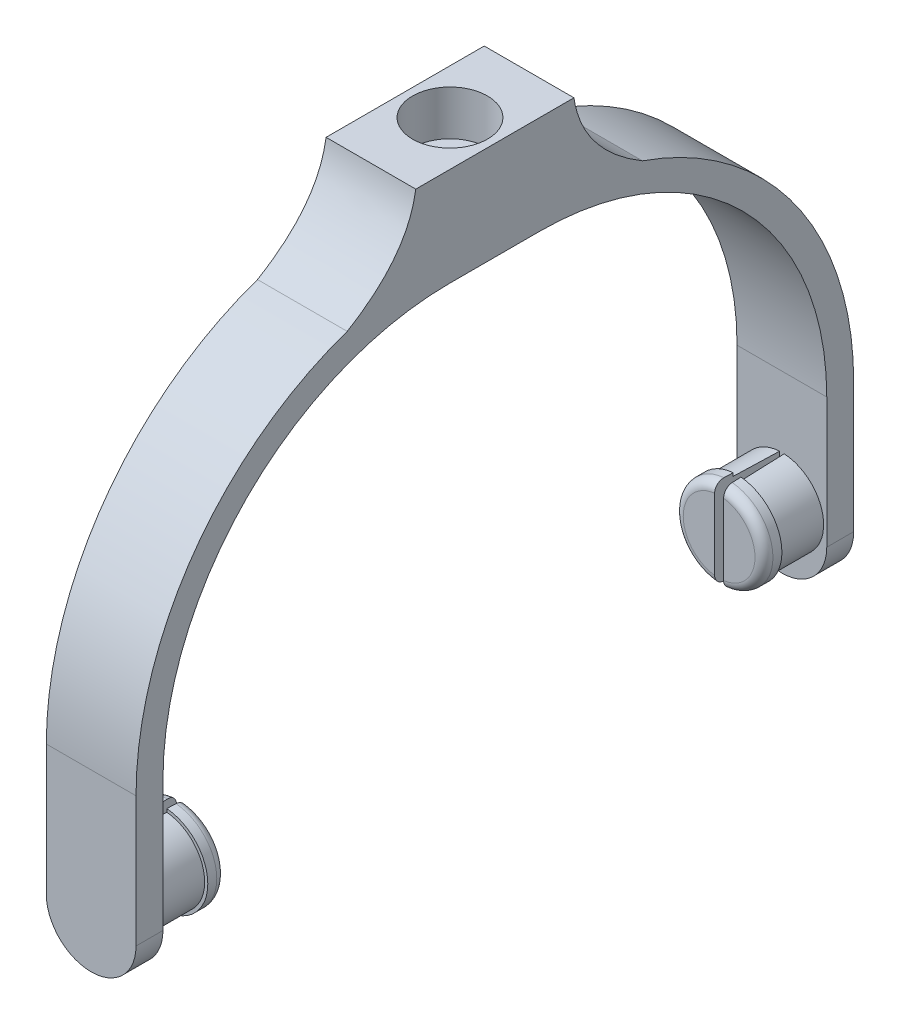
SolidWorks part; units mm, degrees
ref_plane "Front Plane" through (0, 0, 0) normal (0, 0, 1) x (1, 0, 0)
ref_plane "Top Plane" through (0, 0, 0) normal (0, 1, 0) x (1, 0, 0)
ref_plane "Right Plane" through (0, 0, 0) normal (1, 0, 0) x (0, 0, -1)
sketch "Sketch3" plane through (0, 0, 0) normal (1, 0, 0) x (0, 0, -1)
  line L0 (-37, -7) -> (-37, 12.5)
  line L5 (-40, -7) -> (-40, 12.5)
  line L6 (-5, 47.5) -> (5, 47.5)
  line L7 (-5, 44.5) -> (5, 44.5)
  line L8 (37, -7) -> (37, 12.5)
  line L10 (40, -7) -> (40, 12.5)
  line L12 (-37, -7) -> (-40, -7)
  line L13 (37, -7) -> (40, -7)
  line L14 (40, -10) -> (40, 12.5) construction
  line L15 (-40, -10) -> (-40, 12.5) construction
  line L17 (-40, -10) -> (40, -10) construction
  line L18 (-37, -7) -> (37, -7) construction
  arc A4 (-37, 12.5) -> (-5, 44.5) centre (-5, 12.5) cw
  arc A5 (5, 44.5) -> (37, 12.5) centre (5, 12.5) cw
  arc A6 (-40, 12.5) -> (-5, 47.5) centre (-5, 12.5) cw
  arc A7 (5, 47.5) -> (40, 12.5) centre (5, 12.5) cw
  point P0 (0, 0)
  dimension "D1" = 3
  dimension "D2" = 7
extrude "Boss-Extrude1" add sketch "Sketch3" along normal blind 10
fillet "Fillet1" radius 5 4 edges at (10, -7, -38.5) (0, -7, -38.5) (0, -7, 38.5) (10, -7, 38.5)
sketch "Sketch6" plane through (0, 0, 37) normal (0, 0, -1) x (-1, 0, 0)
  line L0 (-5, -7) -> (-5, -2.6229) construction
  circle A2 centre (-5, 0) radius 4.65
  point P0 (0, 0)
  dimension "D1" = 7
extrude "Boss-Extrude2" add sketch "Sketch6" along normal blind 5
sketch "Sketch7" plane through (0, 0, 32) normal (0, 0, -1) x (-1, 0, 0)
  circle A2 centre (-5, 0) radius 5
  circle A3 centre (-5, 0) radius 5
  point P0 (-4.7155, -0.2336)
  point P3 (-4.7155, -0.2336)
  dimension "D1" = 0.35
extrude "Boss-Extrude3" add sketch "Sketch7" along normal blind 2
fillet "Fillet2" radius 1 1 edges at (5, 5, 30)
mirror "Mirror1" about plane through (0, 0, 0) normal (0, 0, 1) of "Boss-Extrude3", "Fillet2", "Boss-Extrude2"
sketch "Sketch8" plane through (10, 0, 0) normal (1, 0, 0) x (0, 0, -1)
  line L1 (8.8152, 55.4795) -> (-8.8152, 55.4795)
  line L5 (0, 47.5) -> (0, 55.4795) construction
  line L13 (37, 12.5) -> (37, -2)
  line L14 (37, -2) -> (40, -2)
  line L15 (40, -2) -> (40, 12.5)
  line L16 (5, 47.5) -> (-5, 47.5)
  line L17 (-40, 12.5) -> (-40, -2)
  line L18 (-40, -2) -> (-37, -2)
  line L19 (-37, -2) -> (-37, 12.5)
  line L20 (-5, 44.5) -> (5, 44.5)
  line L24 (5, 47.5) -> (-5, 47.5)
  arc A0 (5, 47.5) -> (16.4608, 45.5704) centre (5, 12.5) cw
  arc A4 (40, 12.5) -> (5, 47.5) centre (5, 12.5) ccw
  arc A5 (-5, 47.5) -> (-40, 12.5) centre (-5, 12.5) ccw
  arc A6 (-5, 44.5) -> (-37, 12.5) centre (-5, 12.5) ccw
  arc A7 (37, 12.5) -> (5, 44.5) centre (5, 12.5) ccw
  arc A9 (-5, 47.5) -> (-16.4608, 45.5704) centre (-5, 12.5) ccw
  spline S0 degree 2 poles (-16.4608, 45.5704) (-9.6893, 49.5906) (-8.8152, 55.4795) knots 0 0 0 1 1 1
  spline S1 degree 2 poles (16.4608, 45.5704) (9.6893, 49.5906) (8.8152, 55.4795) knots 0 0 0 1 1 1
  dimension "D1" = 0
extrude "Boss-Extrude4" add sketch "Sketch8" against normal up to surface (10 mm away) up to face at (0, 21.146, 0)
sketch "Sketch9" plane through (0, 55.4795, 0) normal (0, 1, 0) x (1, 0, 0)
  line L0 (0, 8.8152) -> (10, -8.8152) construction
  circle A0 centre (5, 0) radius 4.175
  dimension "D1" = 8.35
extrude "Cut-Extrude1" cut sketch "Sketch9" against normal blind 5
sketch "Sketch10" plane through (0, 50.4795, 0) normal (0, 1, 0) x (1, 0, 0)
  circle A0 centre (5, 0) radius 1.175
extrude "Cut-Extrude2" cut sketch "Sketch10" against normal through all
sketch "Sketch12" plane through (0, 0, 30) normal (0, 0, -1) x (-1, 0, 0)
  line L1 (-4.5, -6) -> (-5.5, -6)
  line L2 (-4.5, -6) -> (-4.5, 6)
  line L3 (-4.5, 6) -> (-5.5, 6)
  line L4 (-5.5, -6) -> (-5.5, 6)
  line L5 (-4.5, -6) -> (-5.5, 6) construction
  line L6 (-4.5, 6) -> (-5.5, -6) construction
  point P0 (-5, 0)
  dimension "D1" = 1
  dimension "D2" = 12
extrude "Cut-Extrude3" cut sketch "Sketch12" against normal up to surface (7 mm away) draft 2
sketch "Sketch13" plane through (0, 0, -30) normal (0, 0, 1) x (1, 0, 0)
  line L1 (4.5, -6) -> (5.5, -6)
  line L2 (4.5, -6) -> (4.5, 6)
  line L3 (4.5, 6) -> (5.5, 6)
  line L4 (5.5, -6) -> (5.5, 6)
  line L5 (4.5, -6) -> (5.5, 6) construction
  line L6 (4.5, 6) -> (5.5, -6) construction
  point P0 (5, 0)
  dimension "D1" = 12
  dimension "D2" = 1
extrude "Cut-Extrude4" cut sketch "Sketch13" against normal up to surface (7 mm away) draft 2
